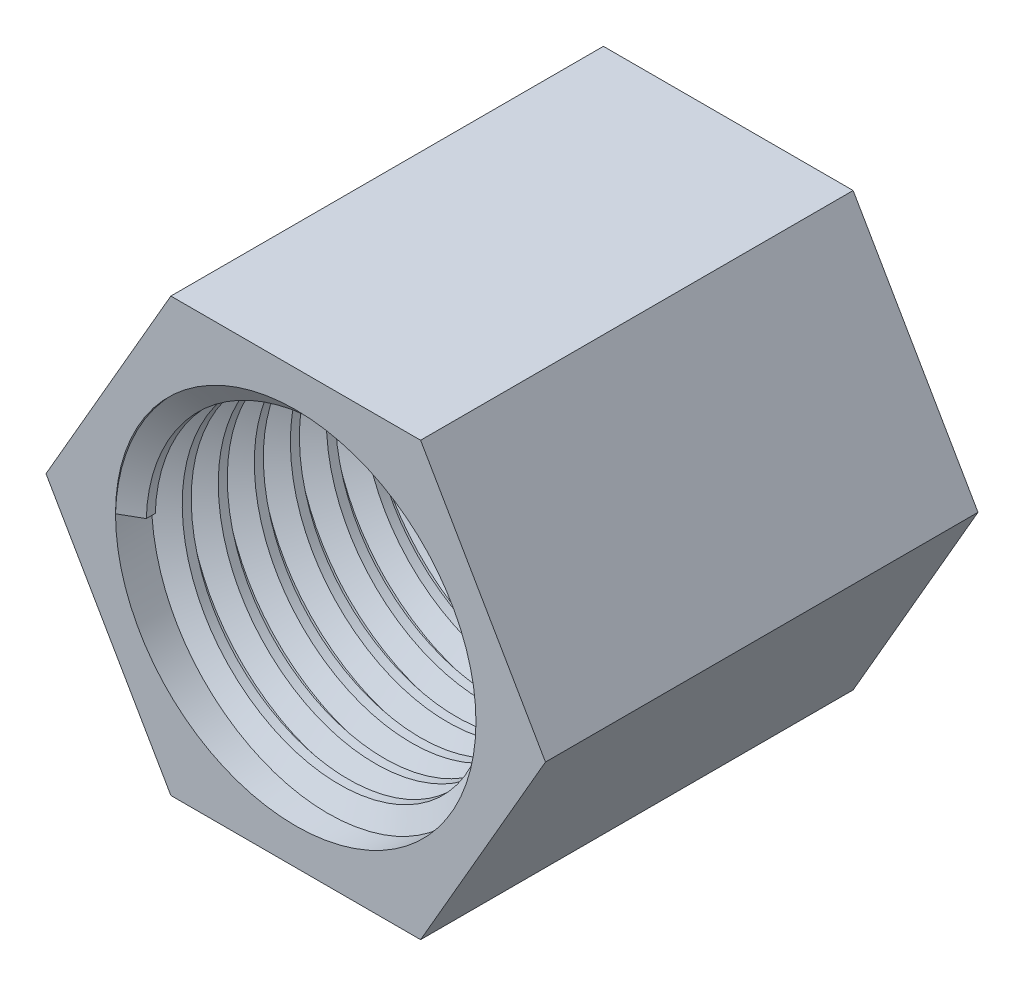
SolidWorks part; units mm, degrees
ref_plane "Front Plane" through (0, 0, 0) normal (0, 0, 1) x (1, 0, 0)
ref_plane "Top Plane" through (0, 0, 0) normal (0, 1, 0) x (1, 0, 0)
ref_plane "Right Plane" through (0, 0, 0) normal (1, 0, 0) x (0, 0, -1)
sketch "Sketch1" plane through (0, 0, 0) normal (0, 0, 1) x (1, 0, 0)
  line L1 (6.9282, 0) -> (3.4641, 6)
  line L2 (3.4641, 6) -> (-3.4641, 6)
  line L3 (-3.4641, 6) -> (-6.9282, 0)
  line L4 (-6.9282, 0) -> (-3.4641, -6)
  line L5 (-3.4641, -6) -> (3.4641, -6)
  line L6 (3.4641, -6) -> (6.9282, 0)
  circle A0 centre (0, 0) radius 6 construction
  dimension "D1" = 12
extrude "Boss-Extrude1" add sketch "Sketch1" along normal blind 12
sketch "Sketch2" plane through (0, 0, 12) normal (0, 0, 1) x (1, 0, 0)
  circle A0 centre (0, 0) radius 5
  dimension "D1" = 10
extrude "Cut-Extrude1" cut sketch "Sketch2" against normal blind 10
thread "Thread1" pitch 1 method extrude profile "Thread Profile1" start angle 0, offset 0, length 10, pitch 1, diameter 10
ref_plane "Plane1" through (-5, 0, 12) normal (0, -1, 0) x (-1, 0, 0)
sketch "Thread Profile1" plane through (-5, 0, 12) normal (0, -1, 0) x (-1, 0, 0)
  line L0 (0, 0) -> (0, 1) construction
  line L11 (0, 0) -> (0, 0.875)
  line L12 (0, 0.875) -> (-0.5413, 0.5625)
  line L13 (-0.5413, 0.5625) -> (-0.5413, 0.3125)
  line L15 (-0.5413, 0.3125) -> (0, 0)
  line L17 (-0.5413, 0.4375) -> (0, 0.4375) construction
  point P2 (0, 0)
  dimension "Pitch" = 1
  dimension "Profile_Angle" = 60
  dimension "Profile_Land" = 0.25
  dimension "Profile_Height" = 0.5413
sketch "Sketch3" plane through (0, 0, 0) normal (0, 0, -1) x (-1, 0, 0)
  circle A0 centre (0, 0) radius 3.5
  dimension "D1" = 7
extrude "Cut-Extrude2" cut sketch "Sketch3" against normal through all
